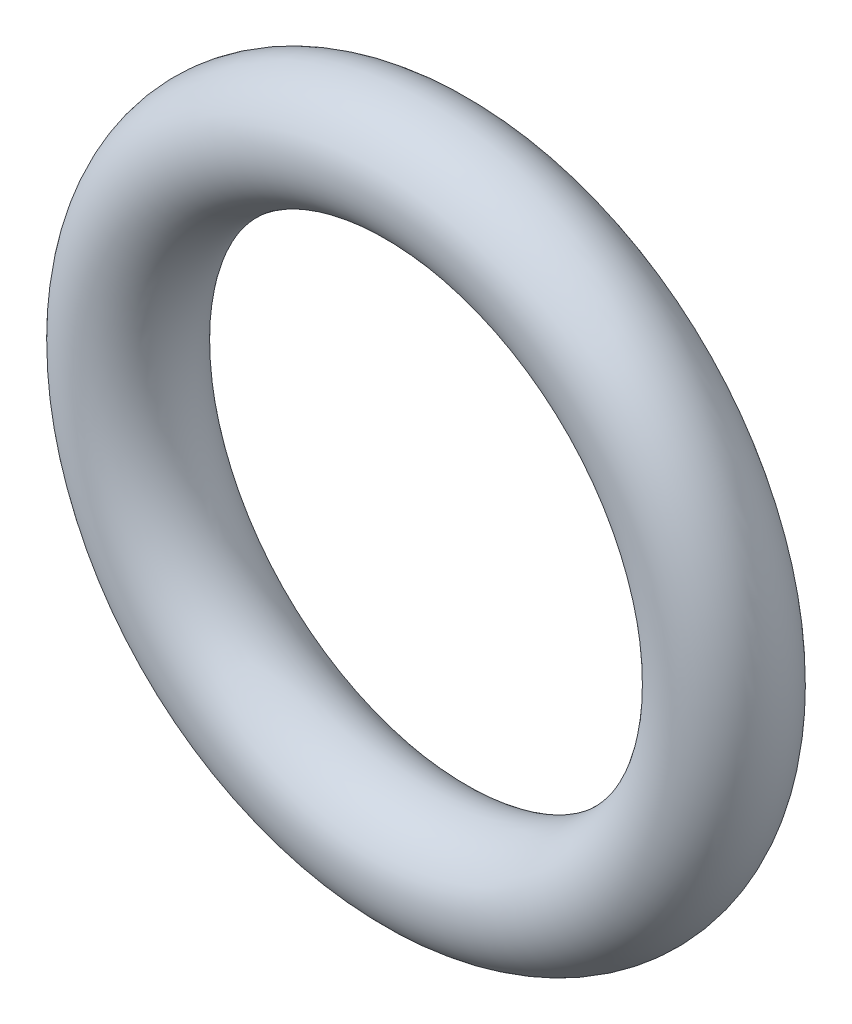
SolidWorks part; units mm, degrees
ref_plane "Front" through (0, 0, 0) normal (0, 0, 1) x (1, 0, 0)
ref_plane "Top" through (0, 0, 0) normal (0, 1, 0) x (1, 0, 0)
ref_plane "Right" through (0, 0, 0) normal (1, 0, 0) x (0, 0, -1)
sketch "Sketch1" plane through (0, 0, 0) normal (0, 0, 1) x (1, 0, 0)
  circle A0 centre (0, 0) radius 3.75
  dimension "d1" = 7.5
sketch "Sketch2" plane through (0, 0, 0) normal (0, 1, 0) x (1, 0, 0)
  circle A0 centre (-4.65, 0) radius 0.9
  point P2 (-3.75, 0)
  dimension "d2" = 1.8
sweep "Sweep1" add profiles "Sketch2" path "Sketch1"
ref_axis "Axis1" through (0, 0, -3.1104) along (0, 0, 1)
